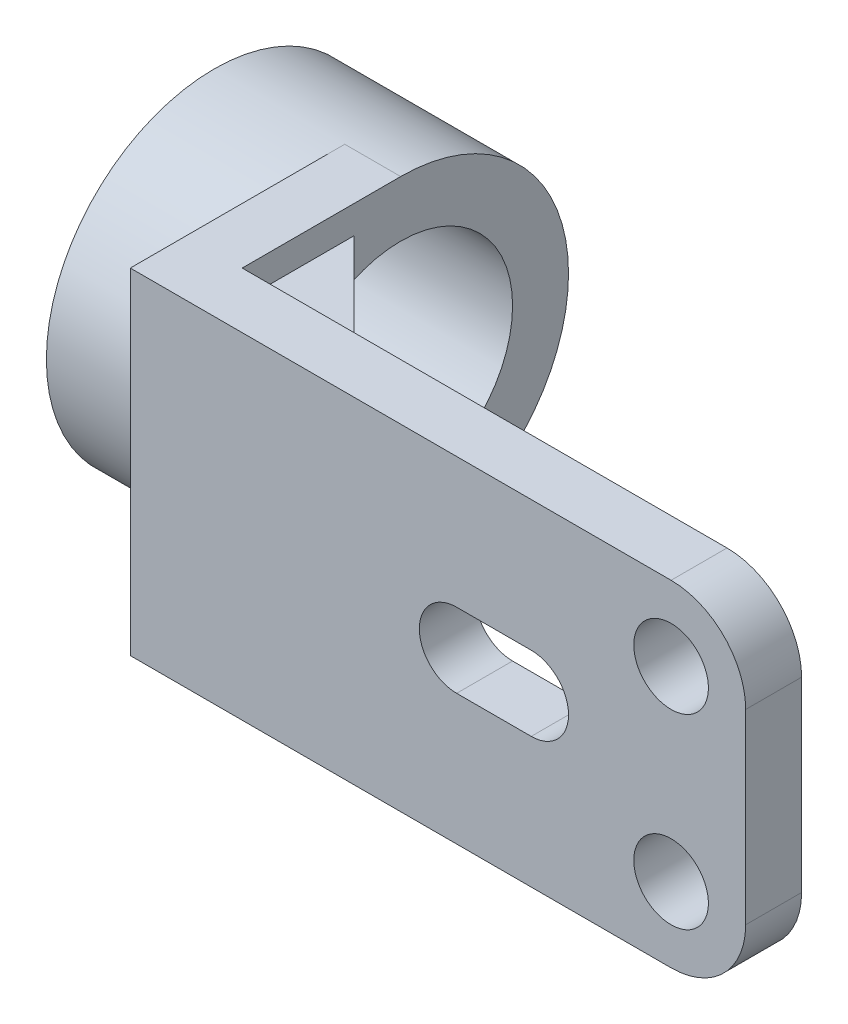
SolidWorks part; units mm, degrees
ref_plane "Front Plane" through (0, 0, 0) normal (0, 0, 1) x (1, 0, 0)
ref_plane "Top Plane" through (0, 0, 0) normal (0, 1, 0) x (1, 0, 0)
ref_plane "Right Plane" through (0, 0, 0) normal (1, 0, 0) x (0, 0, -1)
sketch "Sketch1" plane through (0, 0, 0) normal (0, 1, 0) x (1, 0, 0)
  line L0 (0, 0) -> (0, 26633.4424) construction
  line L1 (0, 0) -> (-26633.4424, 0) construction
  line L2 (0, 0) -> (66, 0)
  line L3 (66, 0) -> (66, 6)
  line L4 (66, 6) -> (6, 6)
  line L5 (6, 6) -> (6, 46)
  line L6 (6, 46) -> (-14, 46)
  line L7 (-14, 46) -> (-14, 14)
  line L8 (-14, 14) -> (0, 14)
  line L9 (0, 14) -> (0, 0)
  line L10 (-14, 30) -> (6, 30) construction
  dimension "D1" = 66
  dimension "D2" = 6
  dimension "D3" = 6
  dimension "D4" = 32
  dimension "D5" = 80
  dimension "D6" = 30
extrude "Boss-Extrude1" add sketch "Sketch1" along normal blind 36
sketch "Sketch2" plane through (0, 36, 0) normal (0, 1, 0) x (1, 0, 0)
  line L0 (0, 14) -> (0, 46)
  line L1 (6, 46) -> (-14, 46) construction
  line L2 (0, 46) -> (-16.1847, 46)
  line L3 (-16.1847, 46) -> (-16.1847, 14)
  line L4 (-16.1847, 14) -> (0, 14)
extrude "Cut-Extrude1" cut sketch "Sketch2" against normal blind 36
sketch "Sketch4" plane through (0, 0, 0) normal (-1, 0, 0) x (0, 0, 1)
  line L0 (-46, 36) -> (0, 0) construction
  line L1 (0, 0) -> (0, 36) construction
  line L2 (0, 36) -> (-46, 0) construction
  line L3 (-23, 36) -> (-46, 36)
  line L4 (-46, 36) -> (-46, 0)
  line L5 (-46, 0) -> (0, 0)
  line L6 (0, 0) -> (0, 36)
  line L7 (0, 36) -> (-23, 36)
  circle A0 centre (-23, 18) radius 18
  circle A1 centre (-23, 18) radius 12
  line M1 (-46, 0) -> (0, 0)
  line M3 (0, 36) -> (-46, 36)
  line M4 (-46, 36) -> (-46, 0)
  dimension "D1" = 24
  dimension "D2" = 36
extrude "Cut-Extrude2" cut sketch "Sketch4" against normal blind 36 contours A0 M3 M4 M1 region at (0, 18, -41.4272)
extrude "Cut-Extrude3" cut sketch "Sketch4<3>" against normal blind 36 contours A1 region at (0, 18, -23)
sketch "Sketch4<3>" plane through (0, 0, 0) normal (-1, 0, 0) x (0, 0, 1) same geometry as "Sketch4"
extrude "Boss-Extrude2" add sketch "Sketch4<4>" along normal blind 14 contours A0 A1 region at (0, 30.3679, -10.6321)
sketch "Sketch4<4>" plane through (0, 0, 0) normal (-1, 0, 0) x (0, 0, 1) same geometry as "Sketch4"
sketch "Sketch5" plane through (0, 0, -6) normal (0, 0, -1) x (-1, 0, 0)
  line L0 (-66, 36) -> (-6, 0) construction
  line L1 (-6, 0) -> (-6, 36) construction
  line L2 (-6, 36) -> (-66, 0) construction
  line L3 (-43, 18) -> (-35, 18) construction
  line L4 (-43, 22) -> (-35, 22)
  line L5 (-43, 14) -> (-35, 14)
  line L6 (-66, 36) -> (-66, 0) construction
  line L7 (-66, 0) -> (-6, 0) construction
  line L8 (-66, 36) -> (-6, 36) construction
  arc A0 (-43, 22) -> (-43, 14) centre (-43, 18) ccw
  arc A1 (-35, 14) -> (-35, 22) centre (-35, 18) ccw
  circle A2 centre (-58, 28) radius 4
  circle A3 centre (-58, 8) radius 4
  point P10 (-39, 18)
  point P25 (0, 0)
  point P27 (-51.953, 5.609)
  dimension "D3" = 4
  dimension "D4" = 18
  dimension "D5" = 8
  dimension "D6" = 8
  dimension "D1" = 8
  dimension "D2" = 23
  dimension "D7" = 8
  dimension "D8" = 8
  dimension "D9" = 8
  dimension "D10" = 8
extrude "Cut-Extrude4" cut sketch "Sketch5" against normal blind 14
fillet "Fillet2" radius 8 2 edges at (66, 36, -3) (66, 0, -3)
sketch "Sketch8" plane through (6, 0, 0) normal (1, 0, 0) x (0, 0, -1)
  line L0 (6, 36) -> (6, 0) construction
  line L1 (6, 29) -> (18, 29)
  line L2 (6, 29) -> (6, 33)
  line L3 (6, 33) -> (18, 33)
  line L4 (18, 29) -> (18, 33)
  line L5 (23, 18) -> (-3.5802, 18) construction
  line L6 (6, 36) -> (23, 36) construction
  line L7 (18, 7) -> (18, 3)
  line L8 (6, 7) -> (18, 7)
  line L9 (6, 7) -> (6, 3)
  line L10 (6, 3) -> (18, 3)
  dimension "D1" = 4
  dimension "D2" = 3
  dimension "D3" = 12
sketch "Sketch9" plane through (0, 0, -6) normal (0, 0, -1) x (-1, 0, 0)
  line L0 (-6, 29) -> (-6, 33) construction
  line L1 (-6, 33) -> (-18, 33)
  line L2 (-6, 33) -> (-6, 29)
  line L3 (-6, 29) -> (-18, 29)
  line L4 (-18, 33) -> (-18, 29)
  line L5 (-6, 7) -> (-6, 3) construction
  line L6 (-6, 7) -> (-18, 7)
  line L7 (-6, 7) -> (-6, 3)
  line L8 (-6, 3) -> (-18, 3)
  line L9 (-18, 7) -> (-18, 3)
  line L10 (-6, 7) -> (-6, 3) construction
  line L11 (-58, 36) -> (-6, 36) construction
  line L12 (-58, 0) -> (-6, 0) construction
  dimension "D1" = 12
  dimension "D2" = 4
  dimension "D3" = 4
  dimension "D4" = 12
  dimension "D5" = 3
  dimension "D6" = 3
extrude "Boss-Extrude3" add sketch "Sketch9" along normal blind 12
sketch "Sketch10" plane through (0, 3, 0) normal (0, -1, 0) x (1, 0, 0)
  line L0 (18, -6) -> (6, -18)
  line L1 (6, -18) -> (14.584, -28.6886)
  line L2 (14.584, -28.6886) -> (24.6038, -16.2049)
  line L3 (24.6038, -16.2049) -> (18, -6)
extrude "Cut-Extrude5" cut sketch "Sketch10" against normal blind 53
